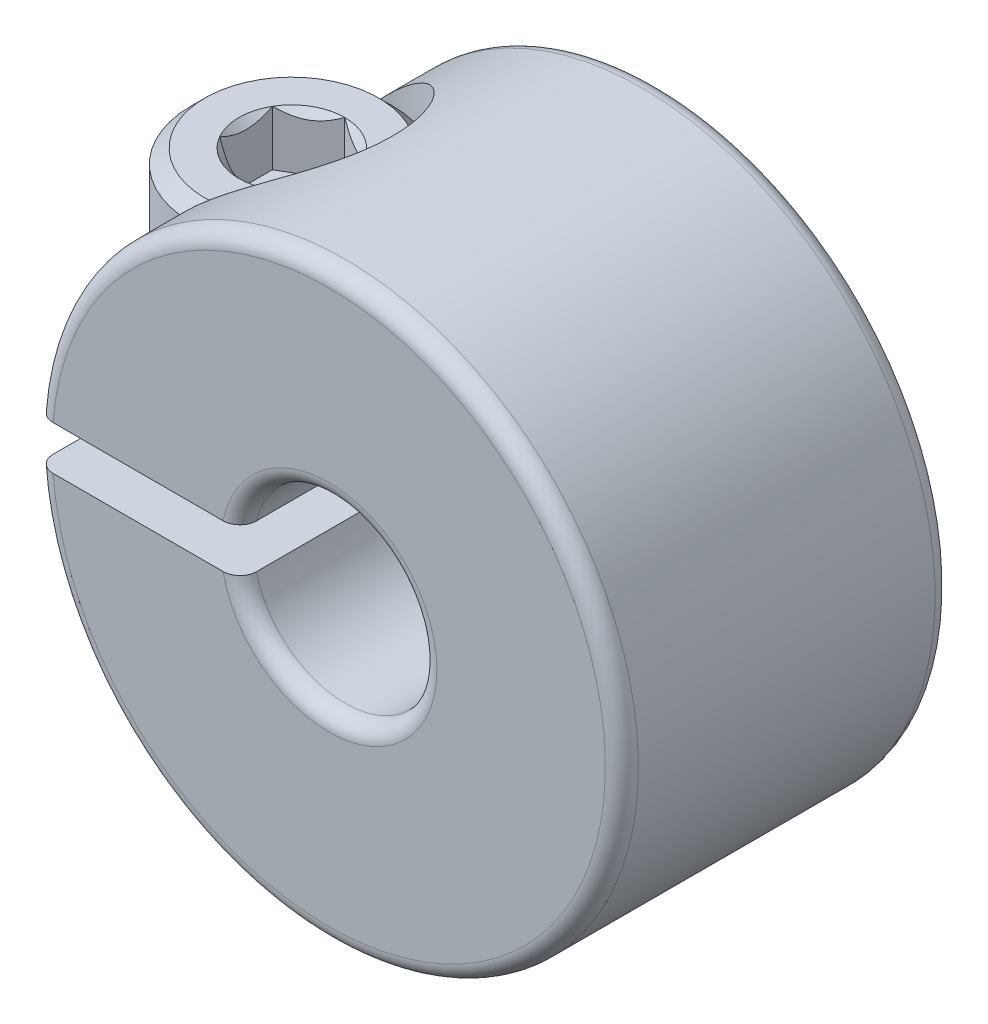
SolidWorks part; units mm, degrees
note: '?' marks a value the reader was unsure of.
ref_plane "Front Plane" through (0, 0, 0) normal (0, 0, 1) x (1, 0, 0)
ref_plane "Top Plane" through (0, 0, 0) normal (0, 1, 0) x (1, 0, 0)
ref_plane "Right Plane" through (0, 0, 0) normal (1, 0, 0) x (0, 0, -1)
sketch "Sketch1" plane through (0, 0, 0) normal (0, 0, 1) x (1, 0, 0)
  line L0 (-8, 0) -> (0, 0) construction
  line L1 (-7.9775, 0.6) -> (-2.4269, 0.6)
  line L2 (-7.9775, -0.6) -> (-2.4269, -0.6)
  line L5 (0, 0) -> (0, 8) construction
  arc A0 (-7.9775, -0.6) -> (-7.9775, 0.6) centre (0, 0) ccw
  arc A1 (-2.4269, -0.6) -> (-2.4269, 0.6) centre (0, 0) ccw
  dimension "Bore Dia" = 5
  dimension "OD" = 16
  dimension "Separation" = 1.2
extrude "Extrude1" add sketch "Sketch1" along normal mid plane 9
sketch "Sketch21" plane through (0, 0, 0) normal (0, 0, 1) x (1, 0, 0)
  circle A1 centre (0, 0) radius 8
  arc A2 (-7.9775, -0.6) -> (-7.9775, 0.6) centre (0, 0) ccw construction
sketch "Sketch25" plane through (0, 0, 0) normal (0, 1, 0) x (1, 0, 0)
  line L0 (-30.6689, -4.5) -> (-16.0682, -4.5) construction
  line L1 (8, 4.5) -> (-7.9775, 4.5) construction
  line L3 (-2.4044, 0) -> (-8, 0) construction
  line L4 (-8, 0) -> (8, 0) construction
  line L5 (0, 0) -> (0.0113, -4.5) construction
  line L7 (-5.2022, 0) -> (-5.2022, 4.119) construction
  line L9 (-7.9775, -4.5) -> (8, -4.5) construction
  line L10 (-5.5832, 4.5) -> (-5.5832, 4.754)
  line L11 (-5.5832, 4.754) -> (-4.8212, 4.754)
  line L12 (-4.8212, 4.754) -> (-4.8212, 4.5)
  line L13 (-5.2022, 4.119) -> (-4.8212, 4.5)
  line L14 (-5.2022, 4.119) -> (-5.5832, 4.5)
  dimension "D1" = 0.254
  dimension "D2" = 0.762
revolve "Cut-Revolve2" cut sketch "Sketch25" angle 360 about L5
sketch "Sketch4" plane through (0, 0, 0) normal (0, 0, 1) x (1, 0, 0)
  line L0 (-5.51, 8) -> (-2.76, 8)
  line L1 (-2.76, 8) -> (-2.76, 2.85)
  line L2 (-2.76, 2.85) -> (-4.01, 2.85)
  line L3 (-4.01, 2.85) -> (-4.01, -8)
  line L4 (-4.01, -8) -> (-5.51, -8)
  line L5 (-5.51, -8) -> (-5.51, 8)
  line L6 (-2.76, 5.85) -> (-8.26, 5.85) construction
  line L7 (-5.51, 8) -> (-5.51, 10.54) construction
  line L8 (-2.76, 8) -> (0, 8) construction
  line L9 (0, -8) -> (-4.01, -8) construction
  line L10 (0, 0) -> (0, 8) construction
  line L11 (-7.9775, 0.6) -> (-2.4269, 0.6) construction
  arc A4 (-7.9775, -0.6) -> (-7.9775, 0.6) centre (0, 0) ccw construction
  point P20 (-5.51, 5.85)
  dimension "D3" = 2.25
  dimension "D5" = 2.54
  dimension "Screw Location" = 5.51
revolve "Cut-Revolve1" cut sketch "Sketch4" angle 360 about L5
sketch "Sketch6" plane through (0, 0, 0) normal (0, 0, 1) x (1, 0, 0)
  line L0 (-5.51, 5.85) -> (-2.76, 5.85)
  line L1 (-2.76, 5.85) -> (-8.26, 5.85) construction
  line L2 (-2.76, 5.85) -> (-2.76, 2.85)
  line L3 (-2.76, 2.85) -> (-4.01, 2.85)
  line L4 (-4.01, 2.85) -> (-4.01, -5.15)
  line L5 (-4.01, 2.85) -> (-4.01, -8) construction
  line L6 (-4.01, -5.15) -> (-5.51, -5.15)
  line L7 (-5.51, -8) -> (-5.51, 8) construction
  line L8 (-5.51, -5.15) -> (-5.51, 5.85)
  line L9 (-4.01, -5.15) -> (-7.01, -5.15) construction
revolve "Revolve1" add sketch "Sketch6" angle 360 about L8
sketch "Sketch7" plane through (0, 5.85, 0) normal (0, 1, 0) x (-1, 0, 0)
  line L1 (5.51, -1.4434) -> (6.76, -0.7217)
  line L2 (6.76, -0.7217) -> (6.76, 0.7217)
  line L3 (6.76, 0.7217) -> (5.51, 1.4434)
  line L4 (5.51, 1.4434) -> (4.26, 0.7217)
  line L5 (4.26, 0.7217) -> (4.26, -0.7217)
  line L6 (4.26, -0.7217) -> (5.51, -1.4434)
  circle A0 centre (5.51, 0) radius 1.25 construction
  circle A1 centre (5.51, 0) radius 2.75 construction
  dimension "Hex" = 2.5
extrude "Cut-Extrude2" cut sketch "Sketch7" against normal blind 1.5
sketch "Sketch15" plane through (0, 5.85, 0) normal (0, 1, 0) x (1, 0, 0)
  circle A0 centre (-5.51, 0) radius 1.4434
extrude "Cut-Extrude3" cut sketch "Sketch15" against normal up to next (1.5 mm away) draft 45
chamfer "Chamfer2" distance 0.381 angle 45 1 edges at (-5.51, 5.85, -2.75)
sketch "Sketch26" plane through (0, 0, -4.5) normal (0, 0, -1) x (-1, 0, 0)
  circle A0 centre (0, 0) radius 2.5 construction
  circle A1 centre (0, 0) radius 8 construction
  arc A2 (7.9775, 0.6) -> (7.9775, -0.6) centre (0, 0) ccw construction
  arc A3 (2.4269, 0.6) -> (2.4269, -0.6) centre (0, 0) ccw construction
fillet "Fillet1" radius 0.45 4 edges at (8, 0, -4.5) (8, 0, 4.5) (2.5, 0, -4.5) (2.5, 0, 4.5)
sketch "Sketch22" plane through (0, -5.15, 0) normal (0, -1, 0) x (1, 0, 0)
  circle A0 centre (-5.51, 0) radius 1.5 construction
  circle A1 centre (-5.51, 0) radius 1.5
curve "Helix/Spiral2" pitch 0.5 height 8.5 turns 17 parameters "Pitch"=0.5
chamfer "Chamfer3" distance 0.5 angle 45 1 edges at (-5.51, -5.15, -1.5)
sketch "Sketch23" plane through (0, 0, 0) normal (0, 0, 1) x (1, 0, 0)
  line L0 (-7.01, -5.15) -> (-7.01, -5.5875)
  line L1 (-7.01, -5.5875) -> (-6.6852, -5.4)
  line L2 (-6.6852, -5.4) -> (-6.6852, -5.3375)
  line L3 (-6.6852, -5.3375) -> (-7.01, -5.15)
  line L4 (-6.6852, -5.3688) -> (-7.01, -5.3688) construction
  line L5 (-6.8476, -5.2438) -> (-6.8476, -5.4938) construction
  dimension "D1" = 0.0625
  dimension "D2" = 0.25
  dimension "D3" = 60
sweep "Cut-Sweep2" cut profiles "Sketch23" path "Helix/Spiral2"
ref_axis "Axis2" through (-5.51, 5.469, 0) along (0, -1, 0)?
ref_axis "Center Axis 1" through (0, 0, 7.1907) along (0, 0, -1)?
ref_plane "Contact Plane 1" through (0, 0, -4.5) normal (0, 0, -1) x (-1, 0, 0)
ref_plane "Contact Plane 2" through (0, 0, 4.5) normal (0, 0, 1) x (1, 0, 0)
equation "\"D1@Cut-Extrude2\" = \"Head Height@Sketch4\"*.5"
equation "\"D3@Sketch4\" = \"Head Height@Sketch4\"*.750"
equation "\"D1@Fillet1\" = \"Width@Extrude1\"*.05"
equation "\"D1@Chamfer3\" = \"Pitch@Helix/Spiral2\""
equation "\"D3@Helix/Spiral2\"=\"Screw Length@Sketch6\"+\"Pitch@Helix/Spiral2\""
equation "\"D1@Sketch23\"=\"Pitch@Helix/Spiral2\"/8"
equation "\"D2@Sketch23\"=\"D1@Sketch23\"*4"
